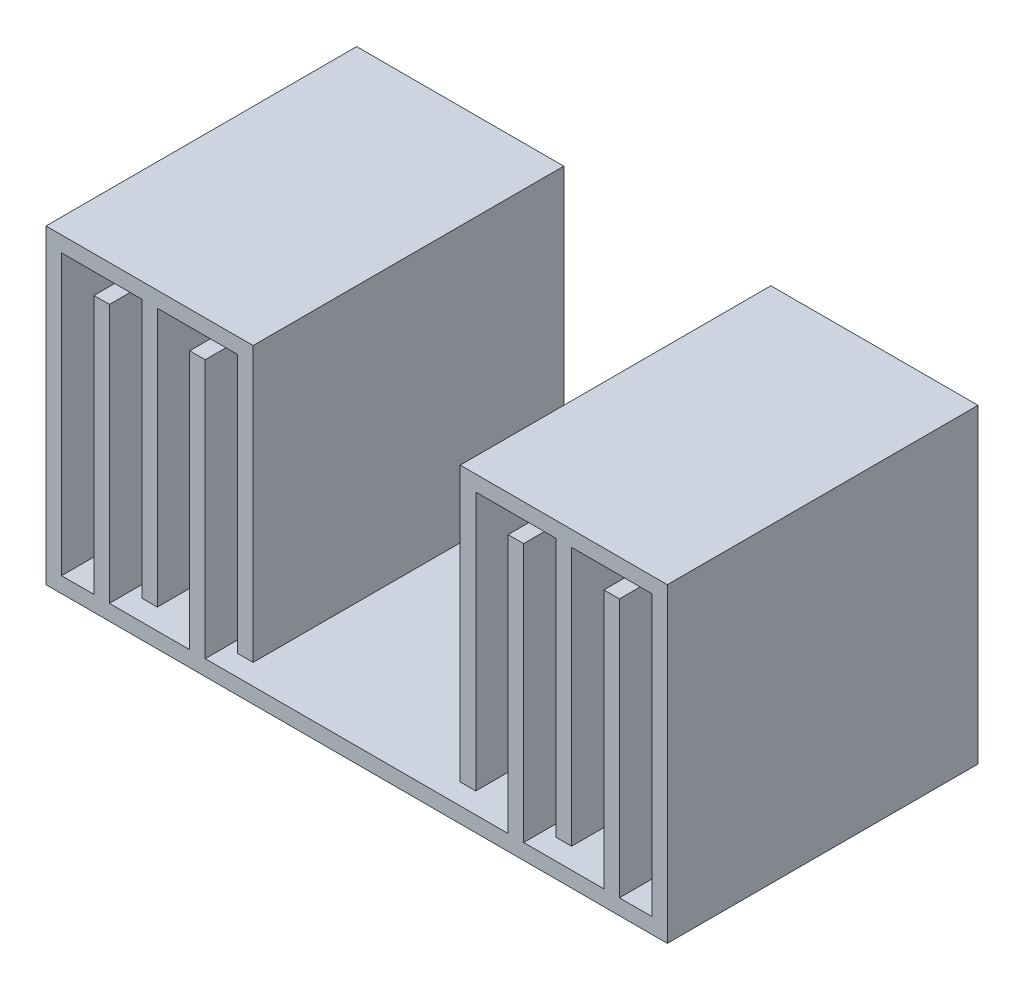
SolidWorks part; units mm, degrees
material "ABS"
ref_plane "Front Plane" through (0, 0, 0) normal (0, 0, 1) x (1, 0, 0)
ref_plane "Top Plane" through (0, 0, 0) normal (0, 1, 0) x (1, 0, 0)
ref_plane "Right Plane" through (0, 0, 0) normal (1, 0, 0) x (0, 0, -1)
sketch "Sketch1" plane through (0, 0, 0) normal (0, 0, 1) x (1, 0, 0)
  line L1 (-30, -15) -> (30, -15)
  line L2 (-30, -15) -> (-30, 15)
  line L3 (-30, 15) -> (30, 15)
  line L4 (30, -15) -> (30, 15)
  line L5 (0, 15) -> (0, -15) construction
  line L6 (-30, 0) -> (30, 0) construction
  point P16 (0, 0)
extrude "Boss-Extrude1" add sketch "Sketch1" against normal blind 30
sketch "Sketch2" plane through (0, 0, 0) normal (0, 0, 1) x (1, 0, 0)
  line L0 (30, 15) -> (-30, 15) construction
  line L1 (-10, -13.5) -> (10, -13.5)
  line L2 (-10, -13.5) -> (-10, 15)
  line L3 (-10, 15) -> (10, 15)
  line L4 (10, -13.5) -> (10, 15)
  line L5 (0, 15) -> (0, -13.5) construction
  line L6 (-10, 0.75) -> (10, 0.75) construction
  point P20 (0, 0.75)
extrude "Cut-Extrude1" cut sketch "Sketch2" against normal through all
sketch "Sketch3" plane through (0, 0, 0) normal (0, 0, 1) x (1, 0, 0)
  line L1 (-28.5, -13.5) -> (-11.5, -13.5)
  line L2 (-28.5, -13.5) -> (-28.5, 13.5)
  line L3 (-28.5, 13.5) -> (-11.5, 13.5)
  line L4 (-11.5, -13.5) -> (-11.5, 13.5)
  line L5 (-20, 13.5) -> (-20, -13.5) construction
  line L6 (-28.5, 0) -> (-11.5, 0) construction
  line L7 (11.5, -13.5) -> (28.5, -13.5)
  line L8 (11.5, -13.5) -> (11.5, 13.5)
  line L9 (11.5, 13.5) -> (28.5, 13.5)
  line L10 (28.5, -13.5) -> (28.5, 13.5)
  line L11 (20, 13.5) -> (20, -13.5) construction
  line L12 (11.5, 0) -> (28.5, 0) construction
  point P16 (-20, 0)
  point P25 (20, 0)
extrude "Cut-Extrude2" cut sketch "Sketch3" against normal blind 28.5
sketch "Sketch4" plane through (0, 0, 0) normal (0, 0, 1) x (1, 0, 0)
  line L0 (-28.5, -13.5) -> (-11.5, -13.5) construction
  line L1 (-16.125, -13.5) -> (-14.625, -13.5)
  line L2 (-16.125, -13.5) -> (-16.125, 11.5)
  line L3 (-16.125, 11.5) -> (-14.625, 11.5)
  line L4 (-14.625, -13.5) -> (-14.625, 11.5)
  line L5 (-15.375, 11.5) -> (-15.375, -13.5) construction
  line L6 (-16.125, -1) -> (-14.625, -1) construction
  line L7 (-11.5, 13.5) -> (-28.5, 13.5) construction
  line L8 (-20.75, -11.5) -> (-19.25, -11.5)
  line L9 (-20.75, -11.5) -> (-20.75, 13.5)
  line L10 (-20.75, 13.5) -> (-19.25, 13.5)
  line L11 (-19.25, -11.5) -> (-19.25, 13.5)
  line L12 (-20, 13.5) -> (-20, -11.5) construction
  line L13 (-20.75, 1) -> (-19.25, 1) construction
  line L14 (11.5, -13.5) -> (28.5, -13.5) construction
  line L15 (-25.375, -13.5) -> (-23.875, -13.5)
  line L16 (-25.375, -13.5) -> (-25.375, 11.5)
  line L17 (-25.375, 11.5) -> (-23.875, 11.5)
  line L18 (-23.875, -13.5) -> (-23.875, 11.5)
  line L19 (-24.625, 11.5) -> (-24.625, -13.5) construction
  line L20 (-25.375, -1) -> (-23.875, -1) construction
  line L21 (14.625, -13.5) -> (16.125, -13.5)
  line L22 (14.625, -13.5) -> (14.625, 11.5)
  line L23 (14.625, 11.5) -> (16.125, 11.5)
  line L24 (16.125, -13.5) -> (16.125, 11.5)
  line L25 (15.375, 11.5) -> (15.375, -13.5) construction
  line L26 (14.625, -1) -> (16.125, -1) construction
  line L27 (28.5, 13.5) -> (11.5, 13.5) construction
  line L28 (19.25, -11.5) -> (20.75, -11.5)
  line L29 (19.25, -11.5) -> (19.25, 13.5)
  line L30 (19.25, 13.5) -> (20.75, 13.5)
  line L31 (20.75, -11.5) -> (20.75, 13.5)
  line L32 (20, 13.5) -> (20, -11.5) construction
  line L33 (19.25, 1) -> (20.75, 1) construction
  line L35 (23.875, -13.5) -> (25.375, -13.5)
  line L36 (23.875, -13.5) -> (23.875, 11.5)
  line L37 (23.875, 11.5) -> (25.375, 11.5)
  line L38 (25.375, -13.5) -> (25.375, 11.5)
  line L39 (24.625, 11.5) -> (24.625, -13.5) construction
  line L40 (23.875, -1) -> (25.375, -1) construction
  point P16 (-15.375, -1)
  point P31 (-20, 1)
  point P38 (-24.625, -1)
  point P47 (15.375, -1)
  point P62 (20, 1)
  point P69 (24.625, -1)
extrude "Boss-Extrude2" add sketch "Sketch4" against normal blind 28.5
sketch "Sketch5" plane through (0, 0, 0) normal (0, 0, 1) x (1, 0, 0)
  line L0 (-10, 15) -> (-10, -13.5) construction
  line L1 (-11.5, -13.5) -> (-10, -13.5)
  line L2 (-11.5, -13.5) -> (-11.5, -11.5)
  line L3 (-11.5, -11.5) -> (-10, -11.5)
  line L4 (-10, -13.5) -> (-10, -11.5)
  line L5 (-10.75, -11.5) -> (-10.75, -13.5) construction
  line L6 (-11.5, -12.5) -> (-10, -12.5) construction
  line L7 (11.5, 13.5) -> (11.5, -13.5) construction
  line L8 (10, -13.5) -> (11.5, -13.5)
  line L9 (10, -13.5) -> (10, -11.5)
  line L10 (10, -11.5) -> (11.5, -11.5)
  line L11 (11.5, -13.5) -> (11.5, -11.5)
  line L12 (10.75, -11.5) -> (10.75, -13.5) construction
  line L13 (10, -12.5) -> (11.5, -12.5) construction
  point P20 (-10.75, -12.5)
  point P32 (10.75, -12.5)
extrude "Cut-Extrude3" cut sketch "Sketch5" against normal blind 28.5
equation "\"W_cell\"= 60mm"
equation "\"H_cell\"= 30mm"
equation "\"D_cell\"= 30mm"
equation "\"W_airway\"= 20mm"
equation "\"t_wall\"= 1.5mm"
equation "\"w_slit_entry\"= 2.0mm"
equation "\"N_passes\"= 4"
equation "\"W_chamber\"= (\"W_cell\" - \"W_airway\") / 2"
equation "\"w_slit\"= (\"W_chamber\" - (\"N_passes\" + 1) * \"t_wall\") / \"N_passes\""
equation "\"L_baffle\"= \"H_cell\" - (2 * \"t_wall\") - \"w_slit_entry\""
equation "\"L_waveguide\"= 100mm"
